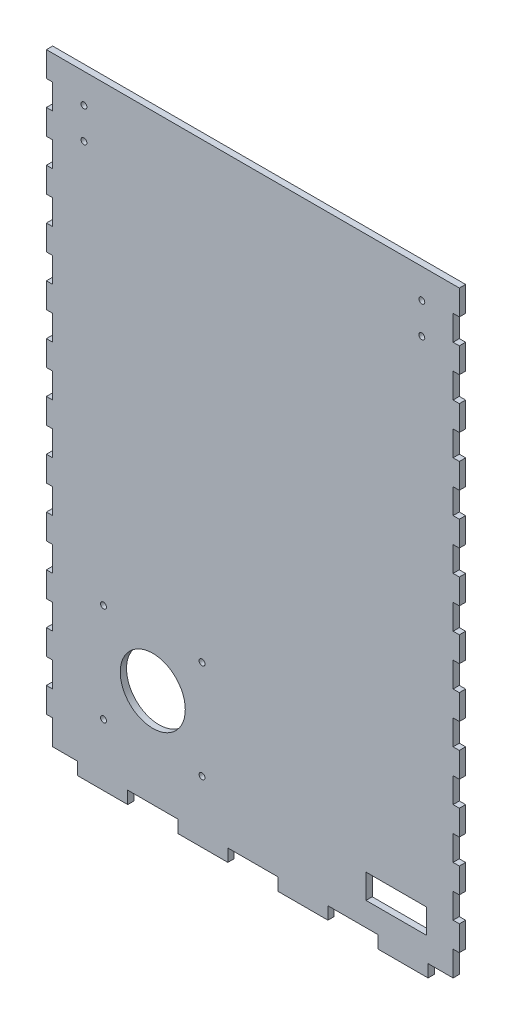
SolidWorks part; units mm, degrees
material "Acrylic (Medium-high impact)"
ref_plane "Front Plane" through (0, 0, 0) normal (0, 0, 1) x (1, 0, 0)
ref_plane "Top Plane" through (0, 0, 0) normal (0, 1, 0) x (1, 0, 0)
ref_plane "Right Plane" through (0, 0, 0) normal (1, 0, 0) x (0, 0, -1)
sketch "Sketch1" plane through (0, 0, 0) normal (0, 0, 1) x (1, 0, 0)
  line L0 (0, 0) -> (203.2, 0)
  line L1 (203.2, 0) -> (203.2, 304.8)
  line L2 (203.2, 304.8) -> (0, 304.8)
  line L3 (0, 304.8) -> (0, 0)
  dimension "D1" = 203.2
  dimension "D2" = 304.8
extrude "Boss-Extrude1" add sketch "Sketch1" along normal blind 3.175
sketch "Sketch2" plane through (0, 0, 3.175) normal (0, 0, 1) x (1, 0, 0)
  line L0 (0, 304.8) -> (-3.175, 304.8)
  line L1 (-3.175, 304.8) -> (-3.175, 292.1)
  line L2 (-3.175, 292.1) -> (0, 292.1)
  line L3 (0, 304.8) -> (0, 0) construction
  line L4 (0, 292.1) -> (0, 304.8)
  line L5 (101.6, 304.8) -> (101.6, 0) construction
  line L6 (203.2, 304.8) -> (0, 304.8) construction
  line L7 (0, 0) -> (203.2, 0) construction
  line L8 (206.375, 292.1) -> (203.2, 292.1)
  line L9 (206.375, 304.8) -> (206.375, 292.1)
  line L10 (203.2, 304.8) -> (206.375, 304.8)
  line L11 (203.2, 292.1) -> (203.2, 304.8)
  line L12 (0, 266.7) -> (0, 279.4)
  line L13 (0, 279.4) -> (-3.175, 279.4)
  line L14 (-3.175, 279.4) -> (-3.175, 266.7)
  line L15 (-3.175, 266.7) -> (0, 266.7)
  line L16 (206.375, 266.7) -> (203.2, 266.7)
  line L17 (203.2, 266.7) -> (203.2, 279.4)
  line L18 (203.2, 279.4) -> (206.375, 279.4)
  line L19 (206.375, 279.4) -> (206.375, 266.7)
  line L20 (0, 241.3) -> (0, 254)
  line L21 (0, 254) -> (-3.175, 254)
  line L22 (-3.175, 254) -> (-3.175, 241.3)
  line L23 (-3.175, 241.3) -> (0, 241.3)
  line L24 (206.375, 241.3) -> (203.2, 241.3)
  line L25 (203.2, 241.3) -> (203.2, 254)
  line L26 (203.2, 254) -> (206.375, 254)
  line L27 (206.375, 254) -> (206.375, 241.3)
  line L28 (0, 215.9) -> (0, 228.6)
  line L29 (0, 228.6) -> (-3.175, 228.6)
  line L30 (-3.175, 228.6) -> (-3.175, 215.9)
  line L31 (-3.175, 215.9) -> (0, 215.9)
  line L32 (206.375, 215.9) -> (203.2, 215.9)
  line L33 (203.2, 215.9) -> (203.2, 228.6)
  line L34 (203.2, 228.6) -> (206.375, 228.6)
  line L35 (206.375, 228.6) -> (206.375, 215.9)
  line L36 (0, 190.5) -> (0, 203.2)
  line L37 (0, 203.2) -> (-3.175, 203.2)
  line L38 (-3.175, 203.2) -> (-3.175, 190.5)
  line L39 (-3.175, 190.5) -> (0, 190.5)
  line L40 (206.375, 190.5) -> (203.2, 190.5)
  line L41 (203.2, 190.5) -> (203.2, 203.2)
  line L42 (203.2, 203.2) -> (206.375, 203.2)
  line L43 (206.375, 203.2) -> (206.375, 190.5)
  line L44 (0, 165.1) -> (0, 177.8)
  line L45 (0, 177.8) -> (-3.175, 177.8)
  line L46 (-3.175, 177.8) -> (-3.175, 165.1)
  line L47 (-3.175, 165.1) -> (0, 165.1)
  line L48 (206.375, 165.1) -> (203.2, 165.1)
  line L49 (203.2, 165.1) -> (203.2, 177.8)
  line L50 (203.2, 177.8) -> (206.375, 177.8)
  line L51 (206.375, 177.8) -> (206.375, 165.1)
  line L52 (0, 139.7) -> (0, 152.4)
  line L53 (0, 152.4) -> (-3.175, 152.4)
  line L54 (-3.175, 152.4) -> (-3.175, 139.7)
  line L55 (-3.175, 139.7) -> (0, 139.7)
  line L56 (206.375, 139.7) -> (203.2, 139.7)
  line L57 (203.2, 139.7) -> (203.2, 152.4)
  line L58 (203.2, 152.4) -> (206.375, 152.4)
  line L59 (206.375, 152.4) -> (206.375, 139.7)
  line L60 (0, 114.3) -> (0, 127)
  line L61 (0, 127) -> (-3.175, 127)
  line L62 (-3.175, 127) -> (-3.175, 114.3)
  line L63 (-3.175, 114.3) -> (0, 114.3)
  line L64 (206.375, 114.3) -> (203.2, 114.3)
  line L65 (203.2, 114.3) -> (203.2, 127)
  line L66 (203.2, 127) -> (206.375, 127)
  line L67 (206.375, 127) -> (206.375, 114.3)
  line L68 (0, 88.9) -> (0, 101.6)
  line L69 (0, 101.6) -> (-3.175, 101.6)
  line L70 (-3.175, 101.6) -> (-3.175, 88.9)
  line L71 (-3.175, 88.9) -> (0, 88.9)
  line L72 (206.375, 88.9) -> (203.2, 88.9)
  line L73 (203.2, 88.9) -> (203.2, 101.6)
  line L74 (203.2, 101.6) -> (206.375, 101.6)
  line L75 (206.375, 101.6) -> (206.375, 88.9)
  line L76 (0, 63.5) -> (0, 76.2)
  line L77 (0, 76.2) -> (-3.175, 76.2)
  line L78 (-3.175, 76.2) -> (-3.175, 63.5)
  line L79 (-3.175, 63.5) -> (0, 63.5)
  line L80 (206.375, 63.5) -> (203.2, 63.5)
  line L81 (203.2, 63.5) -> (203.2, 76.2)
  line L82 (203.2, 76.2) -> (206.375, 76.2)
  line L83 (206.375, 76.2) -> (206.375, 63.5)
  line L84 (0, 38.1) -> (0, 50.8)
  line L85 (0, 50.8) -> (-3.175, 50.8)
  line L86 (-3.175, 50.8) -> (-3.175, 38.1)
  line L87 (-3.175, 38.1) -> (0, 38.1)
  line L88 (206.375, 38.1) -> (203.2, 38.1)
  line L89 (203.2, 38.1) -> (203.2, 50.8)
  line L90 (203.2, 50.8) -> (206.375, 50.8)
  line L91 (206.375, 50.8) -> (206.375, 38.1)
  line L92 (0, 12.7) -> (0, 25.4)
  line L93 (0, 25.4) -> (-3.175, 25.4)
  line L94 (-3.175, 25.4) -> (-3.175, 12.7)
  line L95 (-3.175, 12.7) -> (0, 12.7)
  line L96 (206.375, 12.7) -> (203.2, 12.7)
  line L97 (203.2, 12.7) -> (203.2, 25.4)
  line L98 (203.2, 25.4) -> (206.375, 25.4)
  line L99 (206.375, 25.4) -> (206.375, 12.7)
  line L100 (0, 292.1) -> (0, 266.7) construction
  line L101 (12.7, 0) -> (12.7, -6.35)
  line L102 (12.7, -6.35) -> (38.1, -6.35)
  line L103 (38.1, -6.35) -> (38.1, 0)
  line L104 (38.1, 0) -> (12.7, 0)
  line L105 (88.9, 0) -> (63.5, 0)
  line L106 (63.5, 0) -> (63.5, -6.35)
  line L107 (63.5, -6.35) -> (88.9, -6.35)
  line L108 (88.9, -6.35) -> (88.9, 0)
  line L109 (139.7, 0) -> (114.3, 0)
  line L110 (114.3, 0) -> (114.3, -6.35)
  line L111 (114.3, -6.35) -> (139.7, -6.35)
  line L112 (139.7, -6.35) -> (139.7, 0)
  line L113 (190.5, 0) -> (165.1, 0)
  line L114 (165.1, 0) -> (165.1, -6.35)
  line L115 (165.1, -6.35) -> (190.5, -6.35)
  line L116 (190.5, -6.35) -> (190.5, 0)
  line L117 (38.1, 0) -> (88.9, 0) construction
  dimension "D1" = 3.175
  dimension "D2" = 12.7
  dimension "D4" = 25.4
  dimension "D5" = 12.7
  dimension "D6" = 6.35
  dimension "D7" = 25.4
  dimension "D9" = 50.8
  dimension "D3" = 12
  dimension "D8" = 4
extrude "Boss-Extrude2" add sketch "Sketch2" against normal up to surface (3.175 mm away) up to face at (101.6, 152.4, 0)
sketch "Sketch3" [suppressed] plane through (0, 0, 3.175) normal (0, 0, 1) x (1, 0, 0)
  line L0 (0, 0) -> (-3.175, 0)
  line L1 (-3.175, 0) -> (-3.175, 12.7)
  line L2 (-3.175, 12.7) -> (0, 12.7)
  line L3 (0, 304.8) -> (0, 0) construction
  line L4 (0, 12.7) -> (0, 0)
  line L5 (101.6, 304.8) -> (101.6, 0) construction
  line L6 (203.2, 304.8) -> (0, 304.8) construction
  line L7 (0, 0) -> (203.2, 0) construction
  line L8 (206.375, 12.7) -> (203.2, 12.7)
  line L9 (206.375, 0) -> (206.375, 12.7)
  line L10 (203.2, 0) -> (206.375, 0)
  line L11 (203.2, 12.7) -> (203.2, 0)
  line L12 (0, 38.1) -> (0, 25.4)
  line L13 (0, 25.4) -> (-3.175, 25.4)
  line L14 (-3.175, 25.4) -> (-3.175, 38.1)
  line L15 (-3.175, 38.1) -> (0, 38.1)
  line L16 (206.375, 38.1) -> (203.2, 38.1)
  line L17 (203.2, 38.1) -> (203.2, 25.4)
  line L18 (203.2, 25.4) -> (206.375, 25.4)
  line L19 (206.375, 25.4) -> (206.375, 38.1)
  line L20 (0, 63.5) -> (0, 50.8)
  line L21 (0, 50.8) -> (-3.175, 50.8)
  line L22 (-3.175, 50.8) -> (-3.175, 63.5)
  line L23 (-3.175, 63.5) -> (0, 63.5)
  line L24 (206.375, 63.5) -> (203.2, 63.5)
  line L25 (203.2, 63.5) -> (203.2, 50.8)
  line L26 (203.2, 50.8) -> (206.375, 50.8)
  line L27 (206.375, 50.8) -> (206.375, 63.5)
  line L28 (0, 88.9) -> (0, 76.2)
  line L29 (0, 76.2) -> (-3.175, 76.2)
  line L30 (-3.175, 76.2) -> (-3.175, 88.9)
  line L31 (-3.175, 88.9) -> (0, 88.9)
  line L32 (206.375, 88.9) -> (203.2, 88.9)
  line L33 (203.2, 88.9) -> (203.2, 76.2)
  line L34 (203.2, 76.2) -> (206.375, 76.2)
  line L35 (206.375, 76.2) -> (206.375, 88.9)
  line L36 (0, 114.3) -> (0, 101.6)
  line L37 (0, 101.6) -> (-3.175, 101.6)
  line L38 (-3.175, 101.6) -> (-3.175, 114.3)
  line L39 (-3.175, 114.3) -> (0, 114.3)
  line L40 (206.375, 114.3) -> (203.2, 114.3)
  line L41 (203.2, 114.3) -> (203.2, 101.6)
  line L42 (203.2, 101.6) -> (206.375, 101.6)
  line L43 (206.375, 101.6) -> (206.375, 114.3)
  line L44 (0, 139.7) -> (0, 127)
  line L45 (0, 127) -> (-3.175, 127)
  line L46 (-3.175, 127) -> (-3.175, 139.7)
  line L47 (-3.175, 139.7) -> (0, 139.7)
  line L48 (206.375, 139.7) -> (203.2, 139.7)
  line L49 (203.2, 139.7) -> (203.2, 127)
  line L50 (203.2, 127) -> (206.375, 127)
  line L51 (206.375, 127) -> (206.375, 139.7)
  line L52 (0, 165.1) -> (0, 152.4)
  line L53 (0, 152.4) -> (-3.175, 152.4)
  line L54 (-3.175, 152.4) -> (-3.175, 165.1)
  line L55 (-3.175, 165.1) -> (0, 165.1)
  line L56 (206.375, 165.1) -> (203.2, 165.1)
  line L57 (203.2, 165.1) -> (203.2, 152.4)
  line L58 (203.2, 152.4) -> (206.375, 152.4)
  line L59 (206.375, 152.4) -> (206.375, 165.1)
  line L60 (0, 190.5) -> (0, 177.8)
  line L61 (0, 177.8) -> (-3.175, 177.8)
  line L62 (-3.175, 177.8) -> (-3.175, 190.5)
  line L63 (-3.175, 190.5) -> (0, 190.5)
  line L64 (206.375, 190.5) -> (203.2, 190.5)
  line L65 (203.2, 190.5) -> (203.2, 177.8)
  line L66 (203.2, 177.8) -> (206.375, 177.8)
  line L67 (206.375, 177.8) -> (206.375, 190.5)
  line L68 (0, 215.9) -> (0, 203.2)
  line L69 (0, 203.2) -> (-3.175, 203.2)
  line L70 (-3.175, 203.2) -> (-3.175, 215.9)
  line L71 (-3.175, 215.9) -> (0, 215.9)
  line L72 (206.375, 215.9) -> (203.2, 215.9)
  line L73 (203.2, 215.9) -> (203.2, 203.2)
  line L74 (203.2, 203.2) -> (206.375, 203.2)
  line L75 (206.375, 203.2) -> (206.375, 215.9)
  line L76 (0, 241.3) -> (0, 228.6)
  line L77 (0, 228.6) -> (-3.175, 228.6)
  line L78 (-3.175, 228.6) -> (-3.175, 241.3)
  line L79 (-3.175, 241.3) -> (0, 241.3)
  line L80 (206.375, 241.3) -> (203.2, 241.3)
  line L81 (203.2, 241.3) -> (203.2, 228.6)
  line L82 (203.2, 228.6) -> (206.375, 228.6)
  line L83 (206.375, 228.6) -> (206.375, 241.3)
  line L84 (0, 266.7) -> (0, 254)
  line L85 (0, 254) -> (-3.175, 254)
  line L86 (-3.175, 254) -> (-3.175, 266.7)
  line L87 (-3.175, 266.7) -> (0, 266.7)
  line L88 (206.375, 266.7) -> (203.2, 266.7)
  line L89 (203.2, 266.7) -> (203.2, 254)
  line L90 (203.2, 254) -> (206.375, 254)
  line L91 (206.375, 254) -> (206.375, 266.7)
  line L92 (0, 292.1) -> (0, 279.4)
  line L93 (0, 279.4) -> (-3.175, 279.4)
  line L94 (-3.175, 279.4) -> (-3.175, 292.1)
  line L95 (-3.175, 292.1) -> (0, 292.1)
  line L96 (206.375, 292.1) -> (203.2, 292.1)
  line L97 (203.2, 292.1) -> (203.2, 279.4)
  line L98 (203.2, 279.4) -> (206.375, 279.4)
  line L99 (206.375, 279.4) -> (206.375, 292.1)
  line L100 (0, 12.7) -> (0, 38.1) construction
  line L101 (12.7, 0) -> (12.7, -6.35)
  line L102 (12.7, -6.35) -> (38.1, -6.35)
  line L103 (38.1, -6.35) -> (38.1, 0)
  line L104 (38.1, 0) -> (12.7, 0)
  line L105 (88.9, 0) -> (63.5, 0)
  line L106 (63.5, 0) -> (63.5, -6.35)
  line L107 (63.5, -6.35) -> (88.9, -6.35)
  line L108 (88.9, -6.35) -> (88.9, 0)
  line L109 (139.7, 0) -> (114.3, 0)
  line L110 (114.3, 0) -> (114.3, -6.35)
  line L111 (114.3, -6.35) -> (139.7, -6.35)
  line L112 (139.7, -6.35) -> (139.7, 0)
  line L113 (190.5, 0) -> (165.1, 0)
  line L114 (165.1, 0) -> (165.1, -6.35)
  line L115 (165.1, -6.35) -> (190.5, -6.35)
  line L116 (190.5, -6.35) -> (190.5, 0)
  line L117 (38.1, 0) -> (88.9, 0) construction
  dimension "D1" = 3.175
  dimension "D2" = 12.7
  dimension "D9" = 50.8
  dimension "D3" = 12
  dimension "D8" = 4
  dimension "D4" = 25.4
  dimension "D5" = 6.35
  dimension "D6" = 25.4
  dimension "D7" = 12.7
sketch "Sketch4" plane through (0, 0, 3.175) normal (0, 0, 1) x (1, 0, 0)
  line L0 (50.8, 33.5) -> (50.8, 66.5) construction
  line L1 (34.3, 50) -> (67.3, 50) construction
  line L2 (0, 12.7) -> (0, 0) construction
  line L3 (88.9, 0) -> (114.3, 0) construction
  circle A0 centre (50.8, 50) radius 16.5
  circle A1 centre (25.8, 75) radius 1.5
  circle A5 centre (75.8, 75) radius 1.5
  circle A6 centre (75.8, 25) radius 1.5
  circle A7 centre (25.8, 25) radius 1.5
  dimension "D5" = 33
  dimension "D6" = 3
  dimension "D1" = 50
  dimension "D2" = 50
  dimension "D3" = 50.8
  dimension "D4" = 50
extrude "Cut-Extrude1" cut sketch "Sketch4" against normal up to surface (3.175 mm away) up to face at (101.6, 130.175, 0)
sketch "Sketch5" plane through (0, 0, 0) normal (0, 0, -1) x (-1, 0, 0)
  line L1 (-206.375, 304.8) -> (-206.375, 292.1) construction
  line L2 (-206.375, 304.8) -> (3.175, 304.8) construction
  line L3 (-101.6, 304.8) -> (-101.6, 0) construction
  line L4 (-88.9, 0) -> (-114.3, 0) construction
  circle A1 centre (-187.325, 289.8) radius 1.5
  circle A2 centre (-187.325, 274.05) radius 1.5
  circle A3 centre (-15.875, 274.05) radius 1.5
  circle A4 centre (-15.875, 289.8) radius 1.5
  dimension "D1" = 3
  dimension "D2" = 3
  dimension "D3" = 15.75
  dimension "D4" = 19.05
  dimension "D5" = 15
extrude "Cut-Extrude2" cut sketch "Sketch5" against normal up to surface (3.175 mm away) up to face at (24.3, 25, 3.175)
extrude "Boss-Extrude4" [suppressed] add sketch "Sketch3" against normal up to surface (3.175 mm away) up to face at (17.375, 289.8, 0)
sketch "Sketch6" [suppressed] plane through (0, 0, 0) normal (0, 0, -1) x (-1, 0, 0)
  line L1 (-203.2, 304.8) -> (0, 304.8) construction
  line L2 (-101.6, 304.8) -> (-101.6, 0) construction
  line L3 (-88.9, 0) -> (-114.3, 0) construction
  line L4 (-206.375, 292.1) -> (-206.375, 279.4) construction
  circle A0 centre (-187.325, 289.8) radius 1.5
  circle A1 centre (-187.325, 274.05) radius 1.5
  circle A2 centre (-15.875, 274.05) radius 1.5
  circle A3 centre (-15.875, 289.8) radius 1.5
  dimension "D1" = 3
  dimension "D2" = 3
  dimension "D3" = 19.05
  dimension "D4" = 15
  dimension "D5" = 15.75
extrude "Cut-Extrude3" [suppressed] cut sketch "Sketch6" against normal up to surface (3.175 mm away) up to face at (17.375, 289.8, 3.175)
sketch "Sketch7" plane through (0, 0, 3.175) normal (0, 0, 1) x (1, 0, 0)
  line L0 (159.0125, 24.45) -> (159.0125, 12.011)
  line L1 (159.0125, 12.011) -> (189.5875, 12.011)
  line L2 (189.5875, 12.011) -> (189.5875, 24.45)
  line L3 (189.5875, 24.45) -> (159.0125, 24.45)
  line L4 (206.375, 12.7) -> (206.375, 25.4) construction
  line L5 (190.5, 0) -> (203.2, 0) construction
  dimension "D1" = 16.7875
  dimension "D2" = 24.45
  dimension "D3" = 12.439
  dimension "D4" = 30.575
extrude "Cut-Extrude4" cut sketch "Sketch7" against normal up to surface (3.175 mm away) up to face at (17.375, 289.8, 0)
equation "\"wall_thickness\"= 0.125in"
equation "\"base_thickness\"= 0.25in"
equation "\"D1@Boss-Extrude1\"=\"wall_thickness\""
equation "\"D1@Sketch2\"=\"wall_thickness\""
equation "\"D6@Sketch2\"=\"base_thickness\""
equation "\"D1@Sketch3\"=\"wall_thickness\""
equation "\"D5@Sketch3\"=\"base_thickness\""
